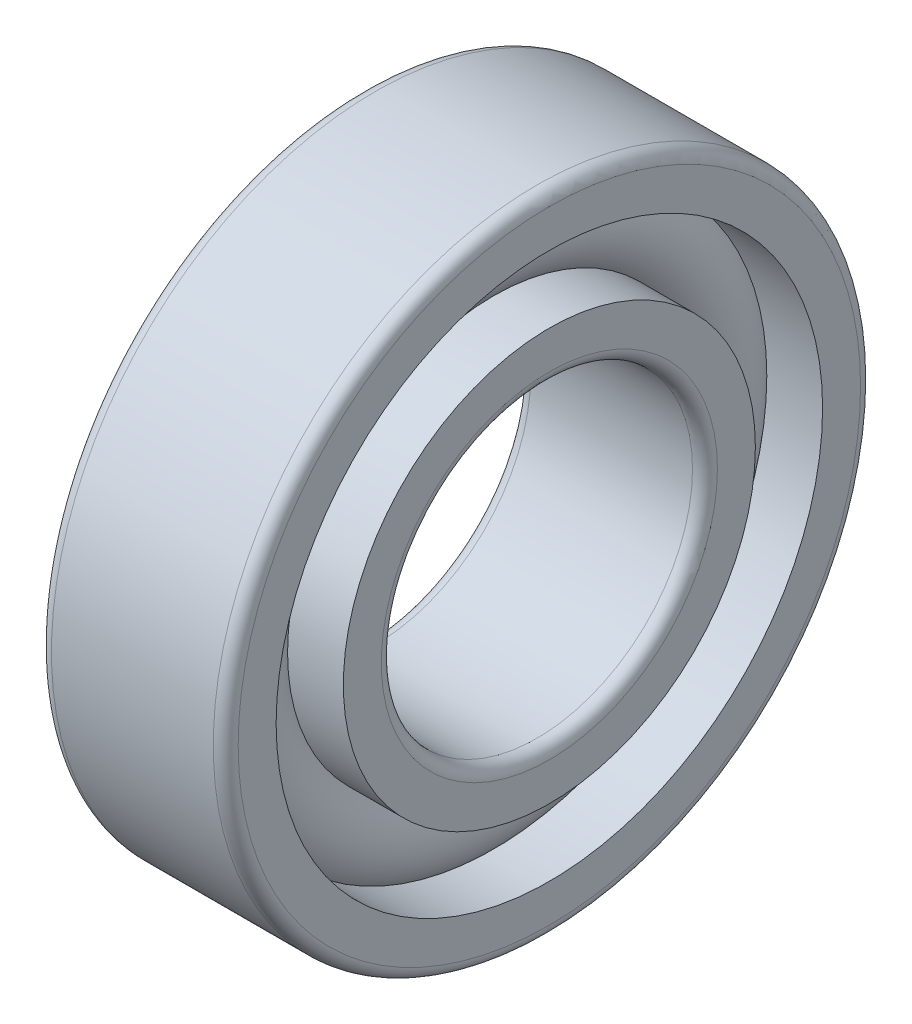
SolidWorks part; units mm, degrees
ref_plane "Plane1" through (0, 0, 0) normal (0, 0, 1) x (1, 0, 0)
ref_plane "Plane2" through (0, 0, 0) normal (0, 1, 0) x (1, 0, 0)
ref_plane "Plane3" through (0, 0, 0) normal (1, 0, 0) x (0, 0, -1)
sketch "Clipboard" plane through (0, 0, 0) normal (0, 0, 1) x (1, 0, 0)
  line L0 (-10, 0) -> (10, 0) construction
  line L1 (0, 0) -> (22.3471, -0.7804)
  line L2 (0, 0) -> (19.2383, 0.6718)
  line L3 (0, 0) -> (22.3471, -0.7804)
  line L4 (0, 0) -> (-22.3573, -0.3902)
  dimension "BallCLRad" = 19.25
sketch "CagSpiSke" plane through (0, 0, 0) normal (0, 0, 1) x (1, 0, 0)
  line L0 (0.405, 18.575) -> (0.405, 19.925)
  line L1 (0.405, 19.925) -> (-0.405, 19.925)
  line L2 (-0.405, 19.925) -> (-0.405, 18.575)
  line L3 (-0.405, 18.575) -> (0.405, 18.575)
  line L4 (-20.6375, 0) -> (20.6375, 0) construction
  line L5 (0, 0) -> (0, 23.7692) construction
  dimension "OD" = 39.85
  dimension "ID" = 37.15
revolve "CageSpine" add sketch "CagSpiSke" angle 0.001 about L4 reverse direction yes
ref_axis "Axis1" through (-50, 0, 0) along (1, 0, 0)
sketch "CagBalSke" plane through (0, 0, 0) normal (0, 0, 1) x (1, 0, 0)
  line L0 (-4.455, 19.25) -> (4.455, 19.25)
  line L1 (-1.905, 19.25) -> (1.905, 19.25) construction
  line L2 (-10, 0) -> (10, 0) construction
  line L3 (0, 0) -> (0, 24) construction
  arc A0 (4.455, 19.25) -> (-4.455, 19.25) centre (0, 19.25) cw
  dimension "BallCLRad" = 19.25
revolve "CageBall" [suppressed] add sketch "CagBalSke" angle 360 about L1 reverse direction yes
pattern_circular "CageBalls" [suppressed] count 2 every 180 about axis through (-50, 0, 0) along (1, 0, 0)
sketch "CagTrmODSke" plane through (0, 0, 0) normal (0, 0, 1) x (1, 0, 0)
  line L0 (4.456, 19.925) -> (4.456, 23.706)
  line L1 (4.456, 23.706) -> (-4.456, 23.706)
  line L2 (-4.456, 23.706) -> (-4.456, 19.925)
  line L3 (-4.456, 19.925) -> (4.456, 19.925)
  line L4 (-20.6375, 0) -> (20.6375, 0) construction
  line L5 (0, 0) -> (0, 25) construction
  dimension "Width" = 8.912
  dimension "ID" = 39.85
  dimension "OD" = 47.412
revolve "CageTrimOD" [suppressed] cut sketch "CagTrmODSke" angle 360 about L4 reverse direction yes
sketch "CagTrmIDSke" plane through (0, 0, 0) normal (0, 0, 1) x (1, 0, 0)
  line L0 (4.456, 14.796) -> (4.456, 18.575)
  line L1 (4.456, 18.575) -> (-4.456, 18.575)
  line L2 (-4.456, 18.575) -> (-4.456, 14.796)
  line L3 (-4.456, 14.796) -> (4.456, 14.796)
  line L4 (-20.6375, 0) -> (20.6375, 0) construction
  line L5 (0, 0) -> (0, 25) construction
  dimension "Width" = 8.912
  dimension "ID" = 29.592
  dimension "OD" = 37.15
revolve "CageTrimID" [suppressed] cut sketch "CagTrmIDSke" angle 360 about L4 reverse direction yes
sketch "BalSimSke" plane through (0, 0, 0) normal (0, 0, 1) x (1, 0, 0)
  line L0 (-10, 0) -> (10, 0) construction
  line L1 (-10, 19.25) -> (10, 19.25) construction
  line L2 (0, 0) -> (0, 23) construction
  circle A0 centre (0, 19.25) radius 4.05
  dimension "BallCLRad" = 19.25
  dimension "Ball_diameter" = 8.1
revolve "BallsSimplified" add sketch "BalSimSke" angle 360 about L0
sketch "BalDetSke" plane through (0, 0, 0) normal (0, 0, 1) x (1, 0, 0)
  line L0 (-4.05, 19.25) -> (4.05, 19.25)
  line L1 (-1.905, 19.25) -> (1.905, 19.25) construction
  line L2 (0, 0) -> (0, 25) construction
  arc A0 (4.05, 19.25) -> (-4.05, 19.25) centre (0, 19.25) cw
  dimension "BallCLRad" = 19.25
  dimension "Ball_diameter" = 8.1
revolve "BallDetailed" [suppressed] add sketch "BalDetSke" angle 360 about L1 reverse direction yes
sketch "InnRacSke" plane through (0, 0, 0) normal (0, 0, 1) x (1, 0, 0)
  line L0 (-2.9851, 16.55) -> (-7.5, 16.55)
  line L1 (-7.5, 16.55) -> (-7.5, 13.5)
  line L2 (-6.5, 12.5) -> (6.5, 12.5)
  line L3 (7.5, 13.5) -> (7.5, 16.55)
  line L4 (7.5, 16.55) -> (2.9851, 16.55)
  line L5 (-20.6375, 0) -> (20.6375, 0) construction
  line L6 (0, 0) -> (0, 30) construction
  arc A0 (-7.5, 13.5) -> (-6.5, 12.5) centre (-6.5, 13.5) ccw
  arc A1 (6.5, 12.5) -> (7.5, 13.5) centre (6.5, 13.5) ccw
  arc A2 (2.9851, 16.55) -> (-2.9851, 16.55) centre (0, 19.25) cw
  dimension "BallCLRad" = 19.25
  dimension "Fillet_radius" = 1
  dimension "Ball_diameter" = 8.05
  dimension "ID" = 25
  dimension "OD" = 33.1
  dimension "Width" = 15
revolve "InnerRace" add sketch "InnRacSke" angle 360 about L5 reverse direction yes
sketch "OutRacSke" plane through (0, 0, 0) normal (0, 0, 1) x (1, 0, 0)
  line L0 (-2.9851, 21.95) -> (-7.5, 21.95)
  line L1 (-7.5, 21.95) -> (-7.5, 25)
  line L2 (-6.5, 26) -> (6.5, 26)
  line L3 (7.5, 25) -> (7.5, 21.95)
  line L4 (7.5, 21.95) -> (2.9851, 21.95)
  line L5 (-20.6375, 0) -> (20.6375, 0) construction
  line L6 (0, 0) -> (0, 30) construction
  arc A0 (-7.5, 25) -> (-6.5, 26) centre (-6.5, 25) cw
  arc A1 (6.5, 26) -> (7.5, 25) centre (6.5, 25) cw
  arc A2 (2.9851, 21.95) -> (-2.9851, 21.95) centre (0, 19.25) ccw
  dimension "BallCLRad" = 19.25
  dimension "Fillet_radius" = 1
  dimension "Ball_diameter" = 8.05
  dimension "Width" = 15
revolve "OuterRace" add sketch "OutRacSke" angle 360 about L5 reverse direction yes
pattern_circular "BallsDetailed" [suppressed] count 2 every 180 about axis through (-50, 0, 0) along (1, 0, 0)
equation "\"BallCLRad@Clipboard\" = ( \"OD@OutRacSke\" + \"ID@InnRacSke\" ) / 4"
equation "\"BallCLRad@BalSimSke\" = \"BallCLRad@Clipboard\""
equation "\"BallCLRad@BalDetSke\" = \"BallCLRad@Clipboard\""
equation "\"BallCLRad@InnRacSke\" = \"BallCLRad@Clipboard\""
equation "\"BallCLRad@OutRacSke\" = \"BallCLRad@Clipboard\""
equation "\"Ball_diameter@InnRacSke\" = \"Ball_diameter@BalDetSke\" - 0.05"
equation "\"Ball_diameter@OutRacSke\" = \"Ball_diameter@BalDetSke\" - 0.05"
equation "\"Ball_diameter@BalSimSke\" = \"Ball_diameter@BalDetSke\""
equation "\"Width@OutRacSke\" = \"Width@InnRacSke\""
equation "\"Fillet_radius@OutRacSke\" = \"Fillet_radius@InnRacSke\""
equation "\"Max_count@Clipboard\" = int( 3.14159265 / atn(( \"Ball_diameter@BalDetSke\" / 2) / sqr( \"BallCLRad@Clipboard\"  *  \"BallCLRad@Clipboard\" - ( \"Ball_diameter@BalDetSke\" / 2) *  ( \"Ball_diameter@BalDetSke\" / 2))))"
equation "\"Max_count@Clipboard\" = ((sgn( \"Max_count@Clipboard\" - \"Count@Clipboard\" )-1)*( \"Max_count@Clipboard\" - \"Count@Clipboard\" ))/-2+ \"Count@Clipboard\""
equation "\"Count@BallsDetailed\" = int( \"Show_count@Clipboard\" ) "
equation "\"Count@BallsDetailed\" = ((sgn( \"Count@BallsDetailed\" - \"Max_count@Clipboard\" )-1)*( \"Count@BallsDetailed\" - \"Max_count@Clipboard\" ))/-2+ \"Max_count@Clipboard\""
equation "\"Count@BallsDetailed\" = ((sgn( \"Count@BallsDetailed\" - \"Min_count@Clipboard\" )+1)*( \"Count@BallsDetailed\" - \"Min_count@Clipboard\"))/2 +\"Min_count@Clipboard\""
equation "\"Angle@BallsDetailed\" = 360.0 / \"Max_count@Clipboard\""
equation "\"BallCLRad@CagBalSke\" = \"BallCLRad@Clipboard\""
equation "\"Count@CageBalls\" = \"Count@BallsDetailed\""
equation "\"Angle@CageBalls\" = \"Angle@BallsDetailed\""
equation "\"Angle@CageSpine\" =  \"Angle@CageBalls\" * ( \"Count@CageBalls\" -1 + int( \"Count@CageBalls\" / \"Max_count@Clipboard\" ) )  + 0.001 -  int( \"Count@CageBalls\" / \"Max_count@Clipboard\" ) * 0.001"
equation "\"Angle@CageSpine\" =  \"Angle@CageSpine\" * int( \"Min_count@Clipboard\" / 2) + int(1 / \"Min_count@Clipboard\")  * 0.001"
equation "\"CageWallOD@CagBalSke\" =  \"Ball_diameter@BalDetSke\" * 1.1"
equation "\"Thickness@CagSpiSke\" =  \"Ball_diameter@BalDetSke\" * 0.1"
equation "\"OD@CagTrmODSke\" = \"BallCLRad@Clipboard\" * 2 + \"CageWallOD@CagBalSke\" + 0.002"
equation "\"ID@CagTrmODSke\" = \"BallCLRad@Clipboard\" * 2 + \"Ball_diameter@BalDetSke\" / 6"
equation "\"OD@CagTrmIDSke\" = \"BallCLRad@Clipboard\" * 2 - \"Ball_diameter@BalDetSke\" / 6"
equation "\"ID@CagTrmIDSke\" = \"BallCLRad@Clipboard\" * 2 - \"CageWallOD@CagBalSke\" + 0.002"
equation "\"OD@CagSpiSke\" = \"ID@CagTrmODSke\""
equation "\"ID@CagSpiSke\" = \"OD@CagTrmIDSke\""
equation "\"Width@CagTrmODSke\" = \"CageWallOD@CagBalSke\" + 0.002"
equation "\"Width@CagTrmIDSke\" = \"CageWallOD@CagBalSke\" + 0.002"
